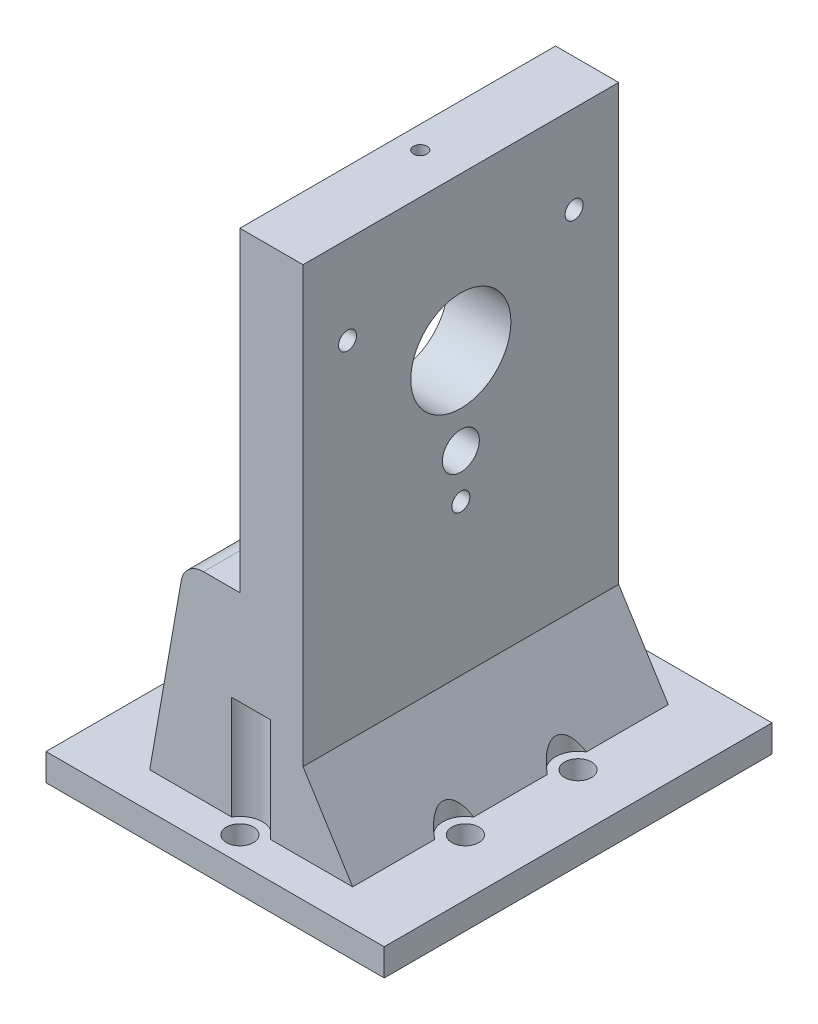
SolidWorks part; units mm, degrees
ref_plane "前视基准面" through (0, 0, 0) normal (0, 0, 1) x (1, 0, 0)
ref_plane "上视基准面" through (0, 0, 0) normal (0, 1, 0) x (1, 0, 0)
ref_plane "右视基准面" through (0, 0, 0) normal (1, 0, 0) x (0, 0, -1)
sketch "草图1" plane through (0, 0, 0) normal (0, 1, 0) x (1, 0, 0)
  line L0 (0, 0) -> (35, 0)
  line L1 (35, 0) -> (35, -70)
  line L2 (35, -70) -> (0, -70)
  line L3 (0, -70) -> (0, 0)
  line L4 (35, 0) -> (40, 0)
  line L5 (40, 0) -> (40, -70)
  line L6 (40, -70) -> (35, -70)
  line L7 (37.5, -70) -> (37.5, 0) construction
  line L8 (40, -70) -> (75, -70)
  line L9 (40, 0) -> (40, -70)
  line L10 (75, -70) -> (75, 0)
  line L11 (75, 0) -> (40, 0)
  line L12 (40, 0) -> (49, 0)
  line L13 (49, 0) -> (49, -70)
extrude "凸台-拉伸1" add sketch "草图1" along normal blind 6 contours L3 L2 L1 L0 | L10 L11 L5 L8 region at (17.5, 0, 35) region at (62, 0, 35)
extrude "凸台-拉伸2" add sketch "草图1<3>" along normal blind 120 contours L7 L6 L5 L4 | L6 L7 L4 L1 | L13 L11 L5 L8 region at (36.25, 0, 35) region at (38.75, 0, 35) region at (44.5, 0, 35)
sketch "草图1<3>" plane through (0, 0, 0) normal (0, 1, 0) x (1, 0, 0) same geometry as "草图1"
sketch "草图3" plane through (35, 0, 0) normal (-1, 0, 0) x (0, 0, 1)
  line L0 (35, 86) -> (35, 66.75)
  line L2 (0, 6) -> (70, 6) construction
  line L3 (35, 6) -> (35, 86)
  line L4 (35, 66.75) -> (35, 57)
  circle A0 centre (35, 86) radius 11.1
  circle A1 centre (35, 66.75) radius 4.1
  circle A2 centre (35, 86) radius 29
  circle A3 centre (35, 57) radius 2
  circle A8 centre (9.8853, 100.5) radius 2
  circle A9 centre (60.1147, 100.5) radius 2
  point P16 (35, 103)
  point P17 (35, 86)
  point P18 (35, 73)
  point P21 (35, 57)
  dimension "D1" = 3
  dimension "D2" = 19.25
sketch "草图4" plane through (0, 0, 0) normal (0, 0, -1) x (-1, 0, 0)
  line L0 (-40, 6) -> (-60, 6)
  line L1 (-75, 6) -> (-49, 6) construction
  line L2 (-60, 6) -> (-40, 38)
  line L4 (-40, 38) -> (-40, 6)
  line L5 (-37.5, 0) -> (-37.5, 35.1786) construction
  line L6 (-35, 0) -> (-40, 0) construction
  line L7 (-15, 6) -> (-35, 38)
  line L8 (-35, 6) -> (-15, 6)
  line L9 (-35, 38) -> (-35, 6)
  line M7 (0, 6) -> (-35, 6)
  line M8 (-35, 6) -> (-35, 120)
extrude "凸台-拉伸4" add sketch "草图4" against normal through all contours L7 M7 M8 | L2 L4 L0 region at (28.3333, 16.6667, 0)
sketch "草图5" plane through (35, 0, 0) normal (-1, 0, 0) x (0, 0, 1)
  line L0 (0, 120) -> (0, 125)
  line L1 (0, 120) -> (0, 38) construction
  line L2 (0, 125) -> (23.3812, 137.5)
  line L3 (35, 120) -> (35, 38) construction
  line L4 (0, 120) -> (70, 120) construction
  line L5 (70, 38) -> (0, 38) construction
  line L6 (23.3812, 137.5) -> (46.6188, 137.5)
  line L7 (0, 120) -> (70, 120)
  line L8 (70, 120) -> (70, 125)
  line L9 (70, 125) -> (46.6188, 137.5)
  point P16 (35, 137.5)
sketch "草图9" plane through (0, 0, 0) normal (0, 0, -1) x (-1, 0, 0)
  line L0 (-35, 120) -> (-15, 6)
  line L1 (-35, 120) -> (-35, 125) construction
  line L2 (-35, 120) -> (-49, 120) construction
  line L5 (-35, 120) -> (-35, 0)
  line L6 (-35, 0) -> (0, 0) construction
  line L7 (-40, 0) -> (-35, 0) construction
  line L8 (-35, 0) -> (-15, 6)
extrude "凸台-拉伸7" add sketch "草图9" against normal through all contours L0 L8 L5
sketch "草图7" plane through (0, 0, 0) normal (0, -1, 0) x (1, 0, 0)
  line L0 (12.5, 70) -> (62.5, 70)
  line L1 (62.5, 22.5) -> (62.5, 47.5)
  line L2 (40, 70) -> (75, 70) construction
  line L3 (62.5, 35) -> (75, 35)
  line L5 (75, 70) -> (75, 0) construction
  line L6 (37.5, 70) -> (37.5, 0)
  circle A6 centre (62.5, 47.5) radius 3
  circle A7 centre (62.5, 22.5) radius 3
  circle A8 centre (12.5, 22.5) radius 3
  circle A9 centre (12.5, 47.5) radius 3
  point P3 (37.5, 70)
  point P12 (62.5, 35)
extrude "切除-拉伸4" cut sketch "草图7" against normal through all contours A9 | A8 | A6 | A7 region at (60.4387, 0, 49.5613) region at (64.5613, 0, 24.5613) region at (12.5, 0, 22.5) region at (12.5, 0, 47.5)
sketch "草图8" plane through (0, 6, 0) normal (0, 1, 0) x (1, 0, 0)
  circle A6 centre (12.5, -47.5) radius 5
  circle A7 centre (12.5, -22.5) radius 5
  circle A8 centre (62.5, -47.5) radius 5
  circle A9 centre (62.5, -22.5) radius 5
  point P8 (62.5, -22.5)
extrude "切除-拉伸5" cut sketch "草图8" along normal blind 115
extrude "切除-拉伸8" cut sketch "草图3" against normal through all both and the other way through all contours A3 | A0 | A8 | A9 | A1
sketch "草图10" plane through (0, 0, 0) normal (0, -1, 0) x (1, 0, 0)
  line L0 (0, 70) -> (0, 94)
  line L1 (0, 94) -> (75, 94)
  line L2 (75, 94) -> (75, 70)
  line L3 (75, 70) -> (0, 70)
extrude "凸台-拉伸8" add sketch "草图10" against normal blind 6 contours L0 L1 L2 L3
sketch "草图11" plane through (0, 6, 0) normal (0, 1, 0) x (1, 0, 0)
  line L0 (37.5, -47.5) -> (37.5, -72.5)
  line L1 (12.5, -47.5) -> (37.5, -47.5)
  line L2 (37.5, -70) -> (37.5, 0) construction
  circle A1 centre (37.5, -72.5) radius 3
extrude "切除-拉伸9" cut sketch "草图11" against normal blind 6 and the other way blind 23 contours A1
ref_plane "基准面1" through (0, 0, 35) normal (0, 0, 1) x (1, 0, 0)
mirror "镜向1" about plane through (0, 0, 35) normal (0, 0, 1) of "凸台-拉伸8", "切除-拉伸9"
sketch "草图12" plane through (0, 120, 0) normal (0, 1, 0) x (1, 0, 0)
  line L0 (35, 0) -> (35, -70)
  line L4 (35, -70) -> (-21.4659, -70)
  line L5 (-21.4659, -70) -> (-21.4659, 0)
  line L6 (-21.4659, 0) -> (35, 0)
extrude "切除-拉伸10" cut sketch "草图12" against normal blind 70 contours L5 L6 L0 L4
fillet "圆角1" radius 5 1 edges at (22.7193, 50, 35)
sketch "草图13" plane through (0, 6, 0) normal (0, 1, 0) x (1, 0, 0)
  circle A0 centre (37.5, -72.5) radius 5
  circle A1 centre (37.5, 2.5) radius 5
extrude "切除-拉伸11" cut sketch "草图13" along normal blind 23
sketch "草图14" plane through (0, 6, 0) normal (0, 1, 0) x (1, 0, 0)
  line L0 (0, 24) -> (0, 8)
  line L1 (0, -94) -> (0, 24) construction
  line L2 (0, 8) -> (75, 8)
  line L3 (75, -94) -> (75, 24) construction
  line L4 (75, 8) -> (75, 24)
  line L5 (75, 24) -> (0, 24)
  line L6 (0, -94) -> (0, -78)
  line L7 (0, -78) -> (75, -78)
  line L8 (75, -78) -> (75, -94)
  line L9 (75, -94) -> (0, -94)
extrude "切除-拉伸12" cut sketch "草图14" against normal blind 10
sketch "草图15" plane through (0, 120, 0) normal (0, 1, 0) x (1, 0, 0)
  line L0 (40, 0) -> (40, -70) construction
  circle A0 centre (40, -35) radius 1.5
extrude "切除-拉伸13" cut sketch "草图15" against normal blind 6.25
sketch "草图16" plane through (35, 0, 0) normal (-1, 0, 0) x (0, 0, 1)
  line L0 (35, 120) -> (35, 115)
  line L1 (35, 120) -> (35, 38) construction
  circle A0 centre (35, 86) radius 29 construction
  circle A1 centre (35, 115) radius 1.5
extrude "切除-拉伸14" cut sketch "草图16" against normal blind 6 contours A1 region at (35, 113.9693, 33.9693)
